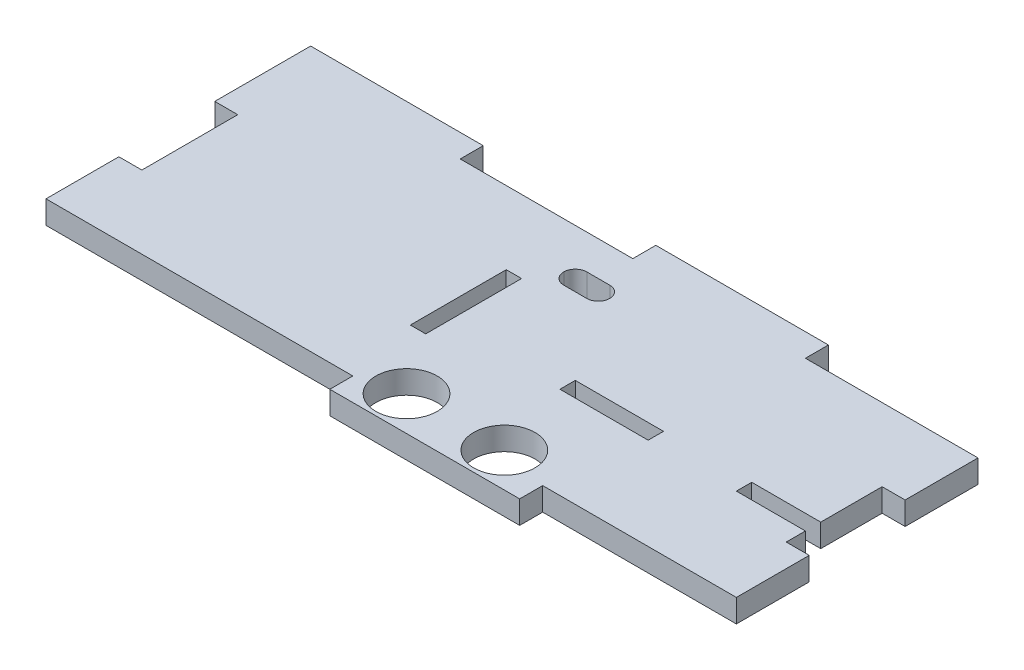
SolidWorks part; units mm, degrees
ref_plane "Front" through (0, 0, 0) normal (0, 0, 1) x (1, 0, 0)
ref_plane "Top" through (0, 0, 0) normal (0, 1, 0) x (1, 0, 0)
ref_plane "Right" through (0, 0, 0) normal (1, 0, 0) x (0, 0, -1)
sketch "Sketch1" plane through (0, 0, 0) normal (0, 1, 0) x (1, 0, 0)
  line L1 (0, 0) -> (180, 0)
  line L2 (0, 0) -> (0, 75)
  line L3 (0, 75) -> (180, 75)
  line L4 (180, 0) -> (180, 75)
  dimension "D1" = 180
  dimension "D2" = 75
extrude "Boss-Extrude1" add sketch "Sketch1" along normal blind 6
sketch "Sketch2" plane through (0, 6, 0) normal (0, 1, 0) x (1, 0, 0)
  line L0 (0, 0) -> (180, 0) construction
  line L5 (180, 0) -> (180, 75) construction
  line L6 (180, 34) -> (156, 34)
  line L7 (180, 34) -> (180, 30)
  line L8 (180, 30) -> (156, 30)
  line L9 (156, 34) -> (156, 30)
  line L10 (180, 75) -> (0, 75) construction
  line L11 (156, 34) -> (133, 34)
  line L12 (156, 34) -> (156, 30)
  line L13 (156, 30) -> (133, 30)
  line L14 (133, 34) -> (133, 30)
  line L15 (133, 34) -> (110, 34)
  line L16 (133, 34) -> (133, 30)
  line L17 (133, 30) -> (110, 30)
  line L18 (110, 34) -> (110, 30)
  line L19 (76, 75) -> (80, 75)
  line L20 (76, 75) -> (76, 50)
  line L21 (76, 50) -> (80, 50)
  line L22 (80, 75) -> (80, 50)
  line L23 (0, 75) -> (0, 0) construction
  line L24 (76, 50) -> (80, 50)
  line L25 (76, 50) -> (76, 25)
  line L26 (76, 25) -> (80, 25)
  line L27 (80, 50) -> (80, 25)
  line L28 (76, 25) -> (80, 25)
  line L29 (76, 25) -> (76, 0)
  line L30 (76, 0) -> (80, 0)
  line L31 (80, 25) -> (80, 0)
  line M9 (180, 0) -> (180, 75)
  dimension "D1" = 4
  dimension "D2" = 24
  dimension "D3" = 23
  dimension "D4" = 23
  dimension "D5" = 30
  dimension "D6" = 4
  dimension "D7" = 25
  dimension "D8" = 76
extrude "Cut-Extrude1" cut sketch "Sketch2" against normal blind 6 contours L15 L18 L17 L14 | L6 L9 L8 M9 | L25 L24 L27 L26 region at (168, 6, -32) region at (121.5, 6, -32)
sketch "Sketch3" plane through (0, 6, 0) normal (0, 1, 0) x (1, 0, 0)
  line L0 (0, 0) -> (180, 0) construction
  line L1 (0, 75) -> (0, 0) construction
  line L3 (84, 60) -> (96, 60)
  line L4 (84, 60) -> (84, 54)
  line L5 (84, 54) -> (96, 54)
  line L6 (96, 60) -> (96, 54)
  line L7 (180, 75) -> (0, 75) construction
  circle A0 centre (91, 9) radius 8
  circle A1 centre (116.5, 9) radius 8
  dimension "D1" = 16
  dimension "D2" = 25.5
  dimension "D3" = 9
  dimension "D4" = 91
  dimension "D5" = 6
  dimension "D6" = 12
  dimension "D7" = 84
  dimension "D8" = 15
extrude "Cut-Extrude5" cut sketch "Sketch3" against normal through all
fillet "Fillet1" radius 3 4 edges at (96, 3, -54) (96, 3, -60) (84, 3, -54) (84, 3, -60)
sketch "Sketch4" plane through (0, 6, 0) normal (0, 1, 0) x (1, 0, 0)
  line L0 (180, 0) -> (180, 30) construction
  line L1 (0, 0) -> (80, 0)
  line L2 (0, 0) -> (0, 6)
  line L3 (0, 6) -> (80, 6)
  line L4 (80, 0) -> (80, 6)
  line L5 (180, 0) -> (129.5, 0)
  line L6 (180, 0) -> (180, 6)
  line L7 (180, 6) -> (129.5, 6)
  line L8 (129.5, 0) -> (129.5, 6)
  line L9 (180, 75) -> (174, 75)
  line L10 (180, 75) -> (180, 50)
  line L11 (180, 50) -> (174, 50)
  line L12 (174, 75) -> (174, 50)
  line L13 (174, 50) -> (180, 50)
  line L14 (174, 50) -> (174, 25)
  line L15 (174, 25) -> (180, 25)
  line L16 (180, 50) -> (180, 25)
  line L18 (174, 25) -> (180, 25)
  line L19 (174, 25) -> (174, 0)
  line L20 (174, 0) -> (180, 0)
  line L21 (180, 25) -> (180, 0)
  line L22 (0, 75) -> (6, 75)
  line L23 (0, 75) -> (0, 50)
  line L24 (0, 50) -> (6, 50)
  line L25 (6, 75) -> (6, 50)
  line L26 (0, 50) -> (6, 50)
  line L27 (0, 50) -> (0, 25)
  line L28 (0, 25) -> (6, 25)
  line L29 (6, 50) -> (6, 25)
  line L30 (0, 25) -> (6, 25)
  line L31 (0, 25) -> (0, 0)
  line L32 (0, 0) -> (6, 0)
  line L33 (6, 25) -> (6, 0)
  line L34 (0, 75) -> (45, 75)
  line L35 (0, 75) -> (0, 69)
  line L36 (0, 69) -> (45, 69)
  line L37 (45, 75) -> (45, 69)
  line L38 (45, 75) -> (90, 75)
  line L39 (45, 75) -> (45, 69)
  line L40 (45, 69) -> (90, 69)
  line L41 (90, 75) -> (90, 69)
  line L42 (90, 75) -> (135, 75)
  line L43 (90, 75) -> (90, 69)
  line L44 (90, 69) -> (135, 69)
  line L45 (135, 75) -> (135, 69)
  line L46 (135, 75) -> (180, 75)
  line L47 (135, 75) -> (135, 69)
  line L48 (135, 69) -> (180, 69)
  line L49 (180, 75) -> (180, 69)
  line M20 (156, 34) -> (180, 34)
  line M21 (180, 34) -> (180, 75)
  line M23 (0, 75) -> (0, 0)
  line M24 (0, 0) -> (180, 0)
  line M25 (180, 0) -> (180, 30)
  line M26 (180, 30) -> (156, 30)
  dimension "D1" = 6
  dimension "D2" = 6
  dimension "D3" = 80
  dimension "D4" = 49.5
  dimension "D5" = 6
extrude "Cut-Extrude6" cut sketch "Sketch4" against normal through all contours L19 L7 L8 M24 | L7 L19 L5 M25 | L14 L15 M25 M26 | L11 L14 M20 M21 | L29 L24 L28 M23 | L33 L3 M23 M24 | L3 L33 L1 L4 | L47 L46 L49 L48 | L39 L38 L41 L40 region at (3, 6, -3) region at (43, 6, -3) region at (3, 6, -37.5) region at (151.75, 6, -3) region at (177, 6, -3) region at (177, 6, -27.5) region at (177, 6, -42)
